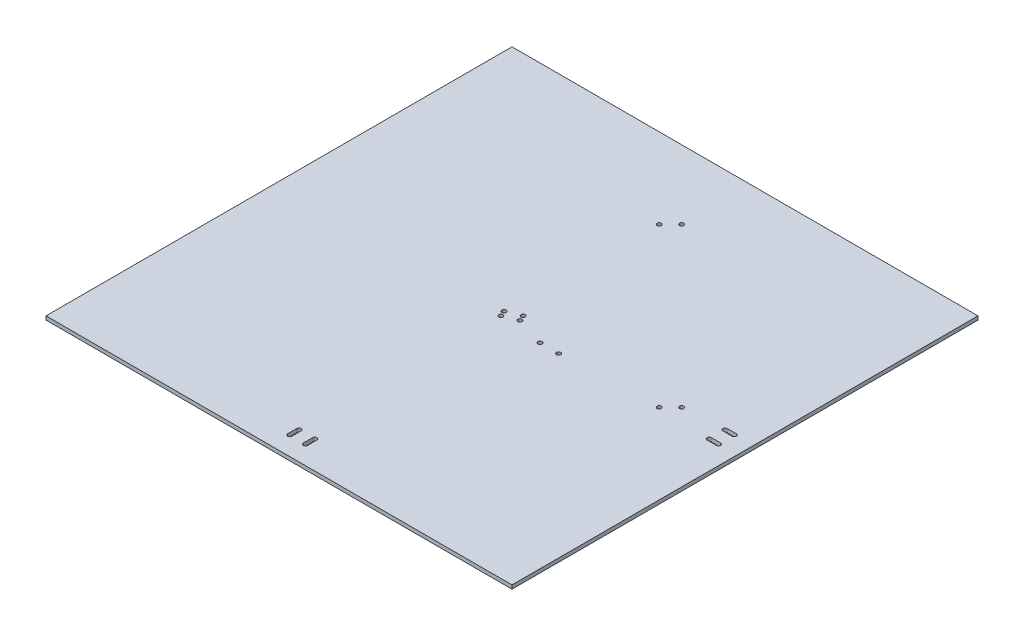
SolidWorks part; units mm, degrees
ref_plane "Plano frontal" through (0, 0, 0) normal (0, 0, 1) x (1, 0, 0)
ref_plane "Plano superior" through (0, 0, 0) normal (0, 1, 0) x (1, 0, 0)
ref_plane "Plano direito" through (0, 0, 0) normal (1, 0, 0) x (0, 0, -1)
sketch "Esboço1" plane through (0, 0, 0) normal (0, 1, 0) x (1, 0, 0)
  line L1 (0, 0) -> (500, 0)
  line L2 (0, 0) -> (0, 500)
  line L3 (0, 500) -> (500, 500)
  line L4 (500, 0) -> (500, 500)
  dimension "D1" = 500
extrude "Ressalto-extrusão1" add sketch "Esboço1" along normal blind 4
sketch "Esboço3" plane through (0, 4, 0) normal (0, 1, 0) x (1, 0, 0)
  line L0 (0, 250) -> (500, 250) construction
  line L1 (0, 500) -> (0, 0) construction
  line L2 (500, 0) -> (500, 500) construction
  line L3 (250, 0) -> (250, 500) construction
  line L4 (0, 0) -> (500, 0) construction
  line L5 (500, 500) -> (0, 500) construction
  line L6 (243.9896, 243.9896) -> (256.0104, 256.0104) construction
  line L7 (241.5, 20) -> (241.5, 30) construction
  line L8 (239.25, 20) -> (239.25, 30)
  line L9 (243.75, 20) -> (243.75, 30)
  line L10 (258.5, 20) -> (258.5, 30) construction
  line L11 (256.25, 20) -> (256.25, 30)
  line L12 (260.75, 20) -> (260.75, 30)
  line L13 (470, 258.5) -> (480, 258.5) construction
  line L14 (470, 260.75) -> (480, 260.75)
  line L15 (470, 256.25) -> (480, 256.25)
  line L16 (470, 241.5) -> (480, 241.5) construction
  line L17 (470, 243.75) -> (480, 243.75)
  line L18 (470, 239.25) -> (480, 239.25)
  circle A0 centre (256.0104, 256.0104) radius 2.25
  circle A1 centre (243.9896, 243.9896) radius 2.25
  circle A2 centre (426.0104, 256.0104) radius 2.25
  circle A3 centre (413.9896, 243.9896) radius 2.25
  circle A4 centre (243.9896, 413.9896) radius 2.25
  circle A5 centre (256.0104, 426.0104) radius 2.25
  circle A6 centre (258.5, 250) radius 2.25
  circle A7 centre (241.5, 250) radius 2.25
  arc A14 (239.25, 20) -> (243.75, 20) centre (241.5, 20) ccw
  arc A15 (243.75, 30) -> (239.25, 30) centre (241.5, 30) ccw
  arc A16 (256.25, 20) -> (260.75, 20) centre (258.5, 20) ccw
  arc A17 (260.75, 30) -> (256.25, 30) centre (258.5, 30) ccw
  arc A20 (470, 260.75) -> (470, 256.25) centre (470, 258.5) ccw
  arc A21 (480, 256.25) -> (480, 260.75) centre (480, 258.5) ccw
  arc A22 (470, 243.75) -> (470, 239.25) centre (470, 241.5) ccw
  arc A23 (480, 239.25) -> (480, 243.75) centre (480, 241.5) ccw
  point P14 (250, 250)
  point P15 (250, 250)
  point P30 (241.5, 25)
  point P48 (258.5, 25)
  point P54 (475, 258.5)
  point P63 (475, 241.5)
  dimension "D3" = 4.5
  dimension "D4" = 4.5
  dimension "D7" = 4.5
  dimension "D8" = 4.5
  dimension "D13" = 2.25
  dimension "D14" = 2.25
  dimension "D21" = 2.25
  dimension "D22" = 2.25
  dimension "D1" = 45
  dimension "D2" = 17
  dimension "D9" = 17
  dimension "D10" = 8.5
  dimension "D15" = 10
  dimension "D16" = 10
  dimension "D17" = 20
  dimension "D18" = 20
  dimension "D19" = 8.5
  dimension "D20" = 8.5
  dimension "D23" = 8.5
  dimension "D24" = 8.5
  dimension "D25" = 10
  dimension "D26" = 10
  dimension "D27" = 20
  dimension "D28" = 20
  dimension "D5" = 2
  dimension "D6" = 2
extrude "Corte-extrusão1" cut sketch "Esboço3" against normal up to surface (4 mm away) up to face at (250, 0, -250)
sketch "Sketch1" plane through (0, 4, 0) normal (0, 1, 0) x (1, 0, 0)
  line L0 (0, 250) -> (500, 250) construction
  line L1 (0, 500) -> (0, 0) construction
  line L2 (500, 0) -> (500, 500) construction
  line L3 (250, 500) -> (250, 0) construction
  line L4 (500, 500) -> (0, 500) construction
  line L5 (0, 0) -> (500, 0) construction
  circle A0 centre (290, 240) radius 2.25
  circle A1 centre (310, 240) radius 2.25
  dimension "D3" = 4.5
  dimension "D4" = 4.5
  dimension "D1" = 40
  dimension "D2" = 20
  dimension "D5" = 20
extrude "Cut-Extrude1" cut sketch "Sketch1" against normal through all
